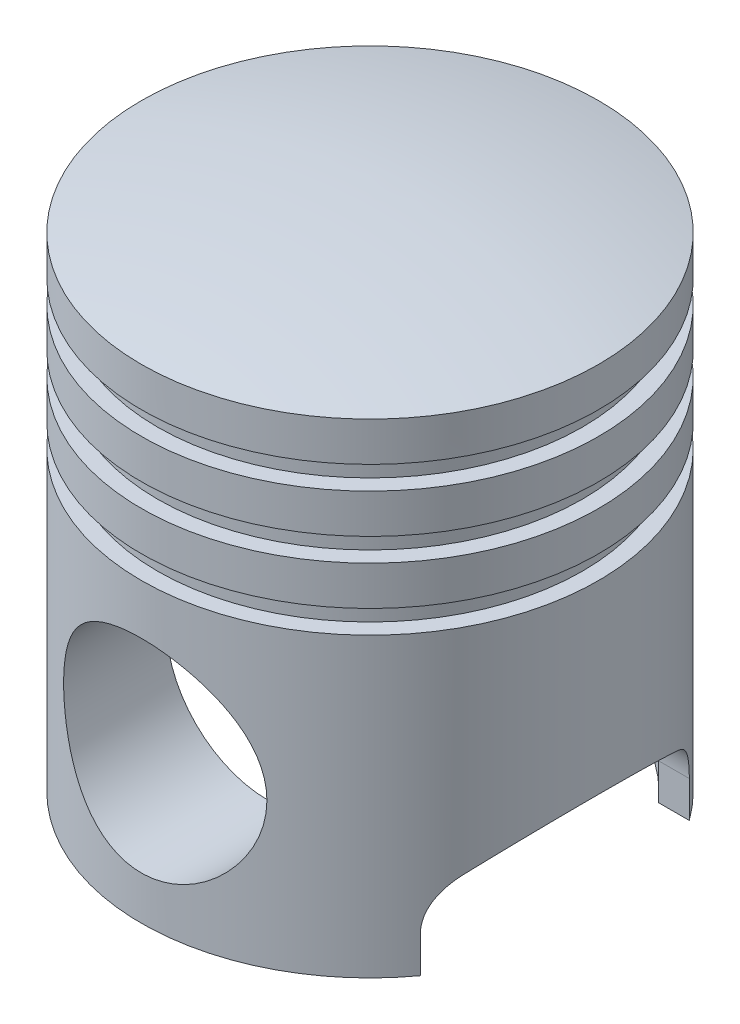
SolidWorks part; units mm, degrees
ref_plane "Front Plane" through (0, 0, 0) normal (0, 0, 1) x (1, 0, 0)
ref_plane "Top Plane" through (0, 0, 0) normal (0, 1, 0) x (1, 0, 0)
ref_plane "Right Plane" through (0, 0, 0) normal (1, 0, 0) x (0, 0, -1)
sketch "Sketch1" plane through (0, 0, 0) normal (0, 1, 0) x (1, 0, 0)
  circle A0 centre (0, 0) radius 42.5
  dimension "D1" = 85
extrude "Boss-Extrude1" add sketch "Sketch1" along normal blind 90
sketch "Sketch2" plane through (0, 90, 0) normal (0, 1, 0) x (1, 0, 0)
  circle A0 centre (0, 0) radius 39.5
  dimension "D1" = 79
extrude "Cut-Extrude2" cut sketch "Sketch2" against normal blind 4.3 from offset 7.3 flip side to cut offset against normal yes
pattern_linear "LPattern1" count 3 spacing 11.6 along (0, -1, 0) of "Cut-Extrude2"
sketch "Sketch3" plane through (0, 0, 0) normal (0, -1, 0) x (1, 0, 0)
  circle A0 centre (0, 0) radius 38
  dimension "D1" = 76
extrude "Cut-Extrude3" cut sketch "Sketch3" against normal blind 85
dome "Dome1" faces to dome 1 distance 5 reverse direction no elliptical dome no face at (0, 90, 42.5) parameters "D1"=5
sketch "Sketch4" plane through (0, 0, 0) normal (0, 0, 1) x (1, 0, 0)
  line L0 (0, 55.2) -> (0, 0) construction
  circle A0 centre (0, 27) radius 18.9
  dimension "D2" = 37.8
  dimension "D1" = 27
extrude "Cut-Extrude4" cut sketch "Sketch4" against normal through all both and the other way through all
sketch "Sketch8" plane through (0, 0, 0) normal (1, 0, 0) x (0, 0, -1)
  line L0 (0, 0) -> (0, 34.0566) construction
  line L1 (-25, 0) -> (-25, 12)
  line L2 (-42.5, 0) -> (42.5, 0) construction
  line L3 (25, 0) -> (25, 12)
  line L4 (-25, 0) -> (25, 0)
  arc A0 (-25, 12) -> (25, 12) centre (0, -19.225) cw
  point P10 (25, 6)
  dimension "D3" = 40
  dimension "D1" = 12
  dimension "D2" = 50
extrude "Cut-Extrude5" cut sketch "Sketch8" against normal through all both and the other way through all
fillet "Fillet1" radius 10 4 edges at (31.4937, 12, 25) (-31.4937, 12, 25) (-31.4937, 12, -25) (31.4937, 12, -25)
sketch "Sketch9" plane through (0, 0, 0) normal (0, 0, 1) x (1, 0, 0)
  circle A0 centre (0, 27) radius 22.5
  circle A1 centre (0, 27) radius 18.9 construction
  circle A2 centre (0, 27) radius 18.9
  dimension "D1" = 45
extrude "Boss-Extrude2" add sketch "Sketch9" along normal up to next from offset 19
mirror "Mirror1" about plane through (0, 0, 0) normal (0, 0, 1) of "Boss-Extrude2"
